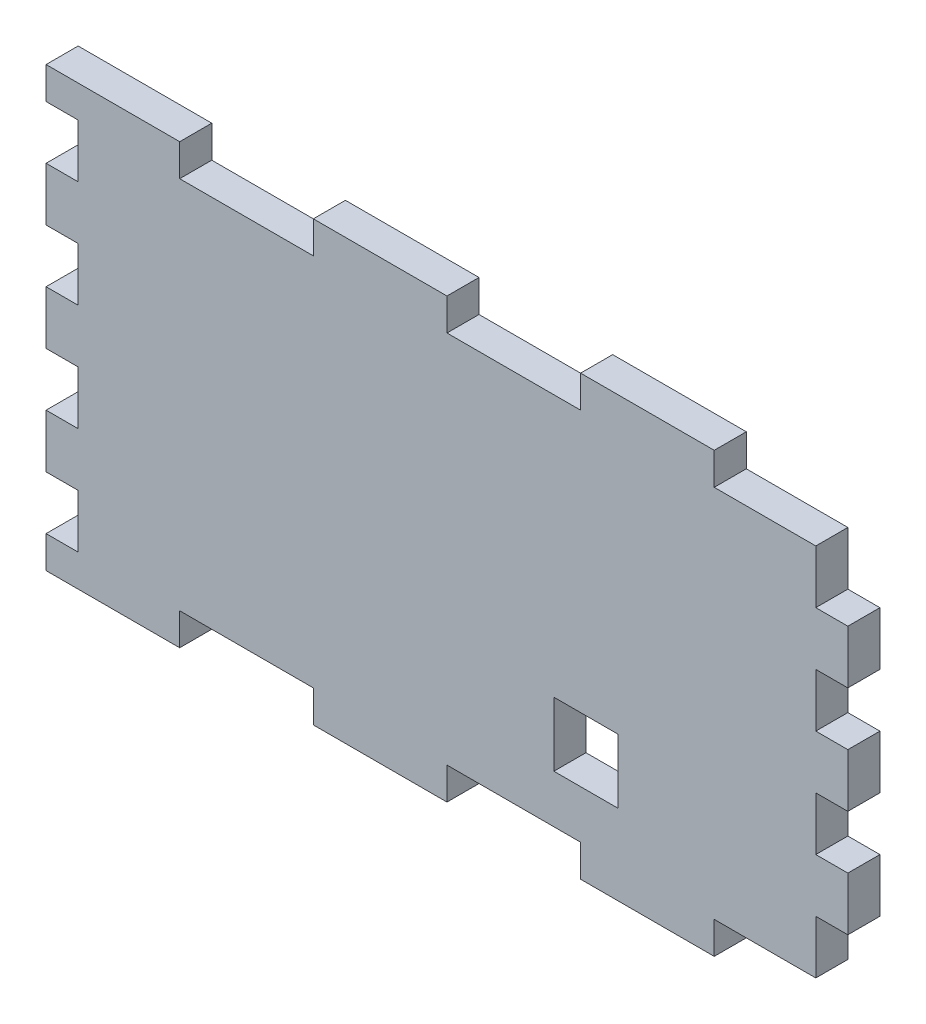
SolidWorks part; units mm, degrees
material "Pine"
ref_plane "Front Plane" through (0, 0, 0) normal (0, 0, 1) x (1, 0, 0)
ref_plane "Top Plane" through (0, 0, 0) normal (0, 1, 0) x (1, 0, 0)
ref_plane "Right Plane" through (0, 0, 0) normal (1, 0, 0) x (0, 0, -1)
sketch "Sketch1" plane through (0, 0, 0) normal (0, 0, 1) x (1, 0, 0)
  line L1 (-75, 41) -> (75, 41)
  line L2 (-75, 41) -> (-75, -41)
  line L3 (-75, -41) -> (75, -41)
  line L4 (75, 41) -> (75, -41)
  line L5 (-75, 41) -> (75, -41) construction
  line L6 (-75, -41) -> (75, 41) construction
  point P0 (0, 0)
  dimension "D1" = 150
  dimension "D2" = 82
extrude "Boss-Extrude1" add sketch "Sketch1" along normal blind 6
sketch "Sketch3" plane through (0, 0, 6) normal (0, 0, 1) x (1, 0, 0)
  line L0 (-75, 41) -> (-75, -41) construction
  line L1 (-75, 35) -> (-69, 35)
  line L2 (-75, 35) -> (-75, 25)
  line L3 (-75, 25) -> (-69, 25)
  line L4 (-69, 35) -> (-69, 25)
  line L5 (75, 41) -> (-75, 41) construction
  line L6 (69, 35) -> (69, 25)
  line L7 (69, 35) -> (75, 35)
  line L8 (75, 35) -> (75, 25)
  line L9 (69, 25) -> (75, 25)
  line L10 (69, 15) -> (69, 5)
  line L11 (69, 15) -> (75, 15)
  line L12 (75, 15) -> (75, 5)
  line L13 (69, 5) -> (75, 5)
  line L14 (-75, 15) -> (-75, 5)
  line L15 (-75, 15) -> (-69, 15)
  line L16 (-69, 15) -> (-69, 5)
  line L17 (-75, 5) -> (-69, 5)
  line L18 (-75, -5) -> (-75, -15)
  line L19 (-75, -5) -> (-69, -5)
  line L20 (-69, -5) -> (-69, -15)
  line L21 (-75, -15) -> (-69, -15)
  line L22 (69, -5) -> (69, -15)
  line L23 (69, -5) -> (75, -5)
  line L24 (75, -5) -> (75, -15)
  line L25 (69, -15) -> (75, -15)
  line L26 (-75, -25) -> (-75, -35)
  line L27 (-75, -25) -> (-69, -25)
  line L28 (-69, -25) -> (-69, -35)
  line L29 (-75, -35) -> (-69, -35)
  line L30 (69, -25) -> (69, -35)
  line L31 (69, -25) -> (75, -25)
  line L32 (75, -25) -> (75, -35)
  line L33 (69, -35) -> (75, -35)
  dimension "D1" = 6
  dimension "D2" = 10
  dimension "D3" = 6
  dimension "D4" = 2
  dimension "D5" = 4
extrude "Cut-Extrude1" cut sketch "Sketch3" against normal blind 10
sketch "Sketch4" plane through (0, 0, 6) normal (0, 0, 1) x (1, 0, 0)
  line L0 (25, -41) -> (25, -35)
  line L1 (75, -41) -> (50, -41)
  line L2 (75, -41) -> (75, -35)
  line L3 (75, -35) -> (50, -35)
  line L4 (50, -41) -> (50, -35)
  line L5 (25, -41) -> (0, -41)
  line L6 (0, -41) -> (0, -35)
  line L7 (25, -35) -> (0, -35)
  line L8 (-25, -41) -> (-25, -35)
  line L9 (-25, -41) -> (-50, -41)
  line L10 (-50, -41) -> (-50, -35)
  line L11 (-25, -35) -> (-50, -35)
  dimension "D1" = 25
  dimension "D2" = 6
  dimension "D3" = 3
extrude "Cut-Extrude2" cut sketch "Sketch4" against normal blind 6
mirror "Mirror1" about plane through (0, 0, 0) normal (0, 1, 0) of "Cut-Extrude2"
sketch "Sketch5" plane through (0, 0, 6) normal (0, 0, 1) x (1, 0, 0)
  line L0 (25, -41) -> (50, -41) construction
  line L1 (20, -14) -> (32, -14)
  line L2 (20, -14) -> (20, -26)
  line L3 (20, -26) -> (32, -26)
  line L4 (32, -14) -> (32, -26)
  line L5 (69, -5) -> (69, -15) construction
  dimension "D1" = 12
  dimension "D2" = 12
  dimension "D3" = 15
  dimension "D4" = 37
extrude "Cut-Extrude3" cut sketch "Sketch5" against normal blind 10
